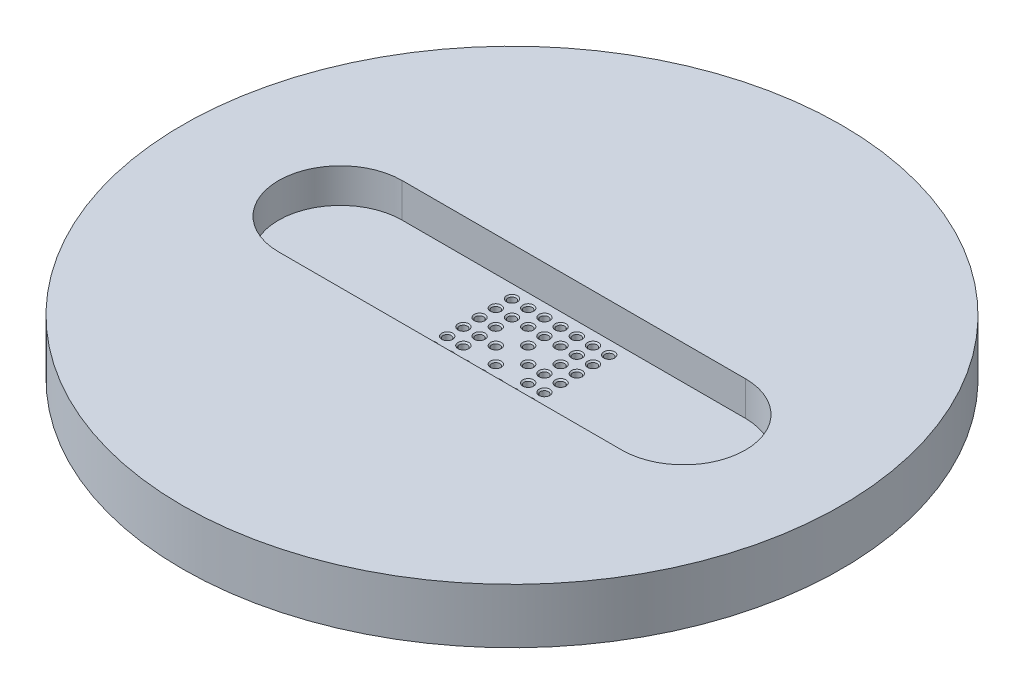
SolidWorks part; units mm, degrees
ref_plane "Front Plane" through (0, 0, 0) normal (0, 0, 1) x (1, 0, 0)
ref_plane "Top Plane" through (0, 0, 0) normal (0, 1, 0) x (1, 0, 0)
ref_plane "Right Plane" through (0, 0, 0) normal (1, 0, 0) x (0, 0, -1)
ref_axis "Axial" through (0, 0.508, 0) along (0, -1, 0)
ref_plane "Bottom Plane" through (0, -10.16, 0) normal (0, 1, 0) x (1, 0, 0)
sketch "Sketch1" plane through (0, 0, 0) normal (0, 1, 0) x (1, 0, 0)
  circle A0 centre (0, 0) radius 60.96
  dimension "D1" = 121.92
extrude "Billet" add sketch "Sketch1" against normal blind 10.16
sketch "Sketch2" plane through (0, 0, 0) normal (0, 1, 0) x (1, 0, 0)
  line L0 (-71.6435, 0) -> (78.9532, 0) construction
  line L1 (-31.75, 11.43) -> (31.75, 11.43)
  line L2 (-31.75, -11.43) -> (31.75, -11.43)
  line L3 (0, 44.5081) -> (0, -98.5298) construction
  arc A4 (-31.75, 11.43) -> (-31.75, -11.43) centre (-31.75, 0) ccw
  arc A5 (31.75, -11.43) -> (31.75, 11.43) centre (31.75, 0) ccw
  dimension "D1" = 22.86
  dimension "D2" = 31.75
extrude "Kerosene Well" cut sketch "Sketch2" against normal blind 6.35
sketch "Sketch4" plane through (0, -10.16, 0) normal (0, 1, 0) x (1, 0, 0)
  line L0 (0, 37.2675) -> (0, -28.2573) construction
  line L1 (-38.2015, 0) -> (37.6086, 0) construction
  circle A0 centre (8.9916, 8.9916) radius 0.7493
  dimension "D1" = 1.4986
  dimension "D2" = 8.9916
  dimension "D3" = 8.9916
extrude "First Kerosene Outlet" cut sketch "Sketch4" along normal up to next
chamfer "Bottom Needle Chamfer" distance 0.254 angle 45 1 edges at (8.9916, -6.35, -8.2423)
pattern_linear "LPattern1" count 7 spacing 2.9972 along (0, 0, 1) count 7 spacing 2.9972 along (-1, 0, 0) skipping (2, 2), (2, 4), (3, 3), (4, 2), (4, 4) of "First Kerosene Outlet", "Bottom Needle Chamfer"
